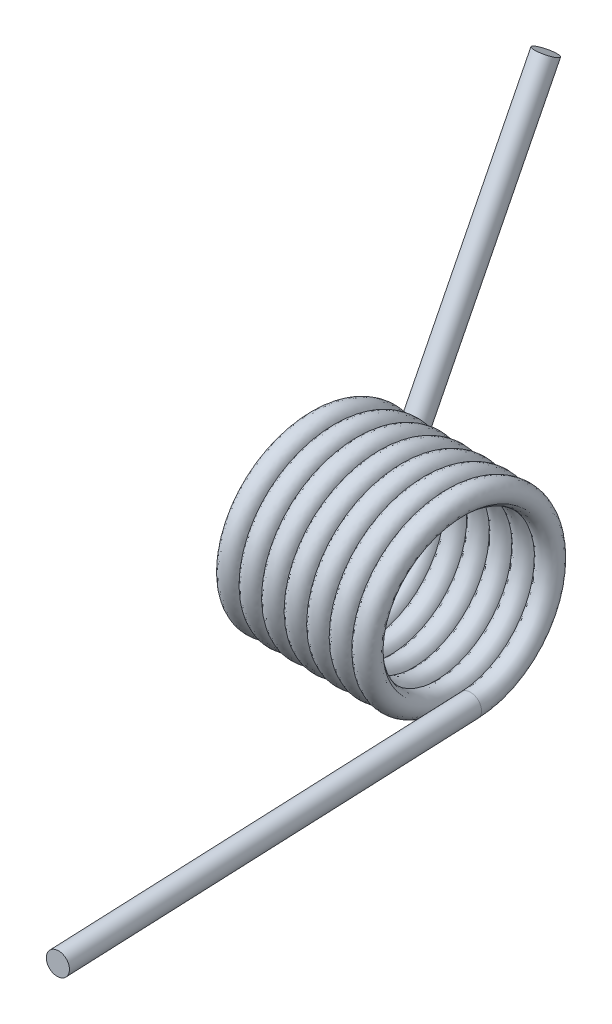
SolidWorks part; units mm, degrees
note: '?' marks a value the reader was unsure of.
ref_plane "Front" through (0, 0, 0) normal (0, 0, 1) x (1, 0, 0)
ref_plane "Top" through (0, 0, 0) normal (0, 1, 0) x (1, 0, 0)
ref_plane "Right" through (0, 0, 0) normal (1, 0, 0) x (0, 0, -1)
sketch "Sketch1" plane through (0, 0, 0) normal (1, 0, 0) x (0, 0, -1)
  line L0 (0, 0) -> (0, -6.6294) construction
  line L1 (0, -6.6294) -> (0, -7.62) construction
  line L2 (0, -7.62) -> (0, -8.6106) construction
  line L3 (0, 8.6106) -> (0, -8.6106) construction
  circle A0 centre (0, 0) radius 6.6294 construction
  circle A1 centre (0, 0) radius 8.6106 construction
  circle A2 centre (0, 0) radius 7.62
  circle A3 centre (0, -7.62) radius 0.9906 construction
  circle A4 centre (0, 0) radius 5.1562 construction
  dimension "Wire Dia" = 1.9812
  dimension "Spring OD" = 17.2212
  dimension "Max Rod OD" = 10.3124
curve "Helix/Spiral1" pitch 2.0066 height 14.3806 turns 7.1667
ref_plane "Plane1" through (0, -7.62, 0) normal (-0.0419, 0, -0.9991) x (0.9988, -0.024, -0.0419)
sketch "Sketch2" plane through (0, -7.62, 0) normal (-0.0419, 0, -0.9991) x (0.9988, -0.024, -0.0419)
  circle A0 centre (0, 0) radius 0.9906
  dimension "D1" = 1.9812
sweep "Sweep1" add profiles "Sketch2" path "Helix/Spiral1"
sketch "Sketch3" plane through (0, 0, 0) normal (0.0419, 0, 0.9991) x (-0.9988, 0.024, 0.0419)
  circle A1 centre (-0.1826, 7.6178) radius 0.9906
  circle A2 centre (-0.1826, 7.6178) radius 0.9906
  dimension "D1" = 0
extrude "Extrude1" add sketch "Sketch3" along normal up to surface (38.3497 mm away)
sketch "Sketch4" plane through (-0.0252, 0.521, -0.3008) normal (-0.0419, 0.8653, -0.4996) x (0.9991, 0.0363, -0.0209)
  circle A1 centre (-14.368, 7.62) radius 0.9906
  circle A2 centre (-14.368, 7.62) radius 0.9906
  dimension "D1" = 0
extrude "Extrude2" add sketch "Sketch4" along normal up to surface (31.75 mm away)
ref_plane "Plane2" through (-0.0252, 0.521, -0.3008) normal (0.0419, -0.8653, 0.4996) x (0.9991, 0.0363, -0.0209)
ref_plane "Plane3" through (0, 0, 0) normal (0.0419, 0, 0.9991) x (0.9991, 0, -0.0419)
ref_axis "Axis1" through (-298.6411, -6.5303, 12.5163) along (0.9988, 0.0242, -0.0419)?
equation "\"D4@Helix/Spiral1\"=\"Wire Dia@Sketch1\"+.001"
equation "\"D1@Sketch2\"=\"Wire Dia@Sketch1\""
